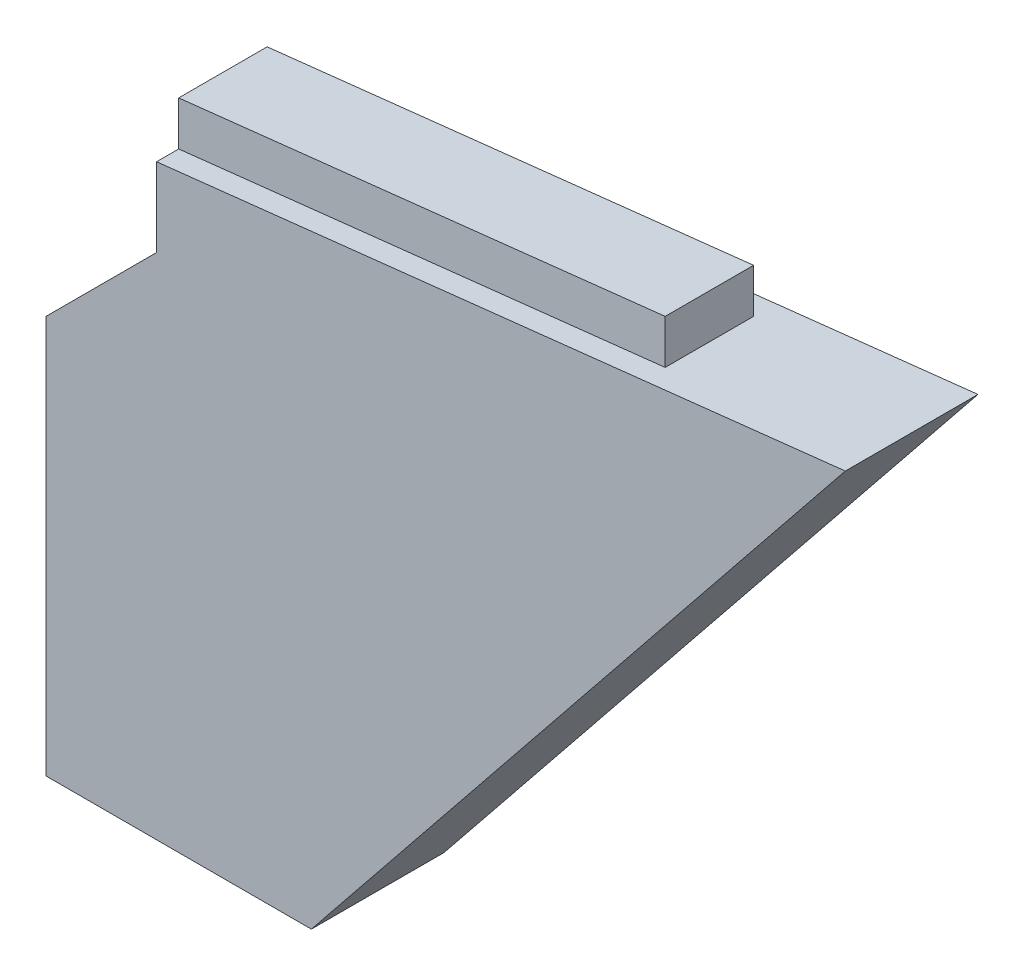
SolidWorks part; units mm, degrees
ref_plane "Front Plane" through (0, 0, 0) normal (0, 0, 1) x (1, 0, 0)
ref_plane "Top Plane" through (0, 0, 0) normal (0, 1, 0) x (1, 0, 0)
ref_plane "Right Plane" through (0, 0, 0) normal (1, 0, 0) x (0, 0, -1)
sketch "Sketch1" plane through (0, 0, 0) normal (0, 0, 1) x (1, 0, 0)
  line L1 (-39.5, -6) -> (-28.5, -6)
  line L13 (-28.5, -4) -> (-28.5, -6)
  line L14 (-39.5, -4) -> (-28.5, -4)
  line L15 (-39.5, -4) -> (-39.5, -6)
  line L16 (-28.5, -4) -> (-28.5, -6)
  line L17 (-36, -20.5) -> (-24.0089, -8.5089)
  line L21 (-42, -20.5) -> (-36, -20.5)
  line L22 (-42, -11.5) -> (-42, -20.5)
  line L23 (-39.5, -9) -> (-42, -11.5)
  line L24 (-39.5, -6) -> (-39.5, -9)
  line L25 (-24.0089, -8.5089) -> (-21.5, -6)
  line L26 (-28.5, -6) -> (-21.5, -6)
  dimension "D1" = 3
  dimension "D2" = 2.5
  dimension "D3" = 9
  dimension "D4" = 6
  dimension "D5" = 7
  dimension "D6" = 11
  dimension "D8" = 2.5
  dimension "D9" = 2
extrude "Boss-Extrude1" add sketch "Sketch1" along normal mid plane 3 contours L1 L24 L23 L22 L21 region at (-34.3533, -12.1467, 0)
extrude "Boss-Extrude2" add sketch "Sketch1<4>" along normal mid plane 2 contours L14 L15 L1 L13 region at (-34, -5, 0)
sketch "Sketch1<4>" plane through (0, 0, 0) normal (0, 0, 1) x (1, 0, 0) same geometry as "Sketch1"
sketch "Sketch2" plane through (0, 0, -1) normal (0, 0, -1) x (-1, 0, 0)
  line L0 (39.5, -6) -> (39.5, -4)
  line L1 (39.5, -4) -> (39.5, -6) construction
  line L2 (39.5, -4) -> (28.5, -4) construction
  line L3 (39.5, -4) -> (21.5, -4)
  line L4 (21.5, -4) -> (39.5, -6)
  line L5 (28.5, -6) -> (10.5, -4)
  line L6 (10.5, -4) -> (28.5, -4)
  line L7 (28.5, -4) -> (28.5, -6) construction
  line L8 (21.5, -6) -> (19.5, -4)
  line L9 (36, -20.5) -> (21.5, -6) construction
  line L10 (28.5, -6) -> (21.5, -6)
  line L11 (28.5, -6) -> (39.5, -7.2222)
  line L12 (39.5, -6) -> (39.5, -9) construction
  line L13 (28.5, -6) -> (39.5, -6)
  line L14 (39.5, -6) -> (39.5, -7.2222)
  line M8 (28.5, -6) -> (39.5, -6)
  dimension "D1" = 2
  dimension "D2" = 18
  dimension "D3" = 2
extrude "Boss-Extrude3" add sketch "Sketch2" against normal blind 2.5 and the other way blind 0.5 contours L10 L5 L8 region at (-23.5417, -5.7083, -1)
extrude "Cut-Extrude1" cut sketch "Sketch2<3>" along normal blind 2.5 contours L14 L11 M8 region at (-35.8333, -6.4074, -1)
sketch "Sketch2<3>" plane through (0, 0, -1) normal (0, 0, -1) x (-1, 0, 0) same geometry as "Sketch2"
extrude "Cut-Extrude2" cut sketch "Sketch2<4>" against normal blind 2.5 from offset 2 contours L14 L11 M8 region at (-35.8333, -6.4074, -1) offset against normal yes
sketch "Sketch2<4>" plane through (0, 0, -1) normal (0, 0, -1) x (-1, 0, 0) same geometry as "Sketch2"
sketch "Sketch3" plane through (0, 0, -1) normal (0, 0, -1) x (-1, 0, 0)
  line L0 (28.5, -4) -> (39.5, -5.2222)
  line L1 (39.5, -4) -> (39.5, -7.2222) construction
  line L2 (39.5, -5.2222) -> (39.5, -4)
  line L3 (39.5, -4) -> (28.5, -4)
  line L6 (28.5, -6) -> (39.5, -7.2222) construction
extrude "Cut-Extrude3" cut sketch "Sketch3" against normal blind 10
sketch "Sketch5" plane through (0.0915, -0.8232, 0) normal (-0.1104, 0.9939, 0) x (0.9939, 0.1104, 0)
  line L1 (-39.8351, 1) -> (-28.7674, 1)
  line L2 (-39.8351, 1) -> (-39.8351, -1)
  line L3 (-39.8351, -1) -> (-28.7674, -1)
  line L4 (-28.7674, 1) -> (-28.7674, -1)
extrude "Cut-Extrude4" cut sketch "Sketch5" along direction (0, -1, 0) on the side against the normal blind 1
sketch "Sketch6" plane through (0, 0, -1.5) normal (0, 0, -1) x (-1, 0, 0)
  line L0 (22.4622, -5.3291) -> (22.2989, -6.7989)
  line L1 (39.5, -7.2222) -> (20.625, -5.125) construction
  line L2 (36, -20.5) -> (20.625, -5.125) construction
  line L3 (22.2989, -6.7989) -> (20.5314, -7.0195)
  line L4 (20.5314, -7.0195) -> (20.0567, -4.9791)
  line L5 (20.0567, -4.9791) -> (21.9153, -4.3024)
  line L6 (21.9153, -4.3024) -> (22.4622, -5.3291)
extrude "Cut-Extrude5" cut sketch "Sketch6" against normal blind 6
sketch "Sketch7" plane through (0, 0, -1.5) normal (0, 0, -1) x (-1, 0, 0)
  line L0 (36, -20.5) -> (23.9264, -5.4918)
  line L1 (39.5, -7.2222) -> (22.4622, -5.3291) construction
  line L2 (23.9264, -5.4918) -> (23.8078, -4.5684)
  line L3 (23.8078, -4.5684) -> (21.9277, -4.3178)
  line L4 (21.9277, -4.3178) -> (19.8806, -6.7827)
  line L5 (19.8806, -6.7827) -> (22.8678, -15.2079)
  line L6 (22.8678, -15.2079) -> (23.3761, -16.0853)
  line L7 (30.534, -21.2658) -> (31.1115, -21.3428)
  line L8 (36, -20.5) -> (24.0445, -17.0044)
  line L9 (24.0445, -17.0044) -> (23.3761, -16.0853)
  line M1 (39.5, -7.2222) -> (22.4622, -5.3291)
  line M2 (22.4622, -5.3291) -> (22.2989, -6.7989)
  line M3 (22.2989, -6.7989) -> (36, -20.5)
extrude "Cut-Extrude6" cut sketch "Sketch7" against normal blind 6 contours L0 M3 M1 M2 region at (-27.1765, -10.6703, -1.5)
